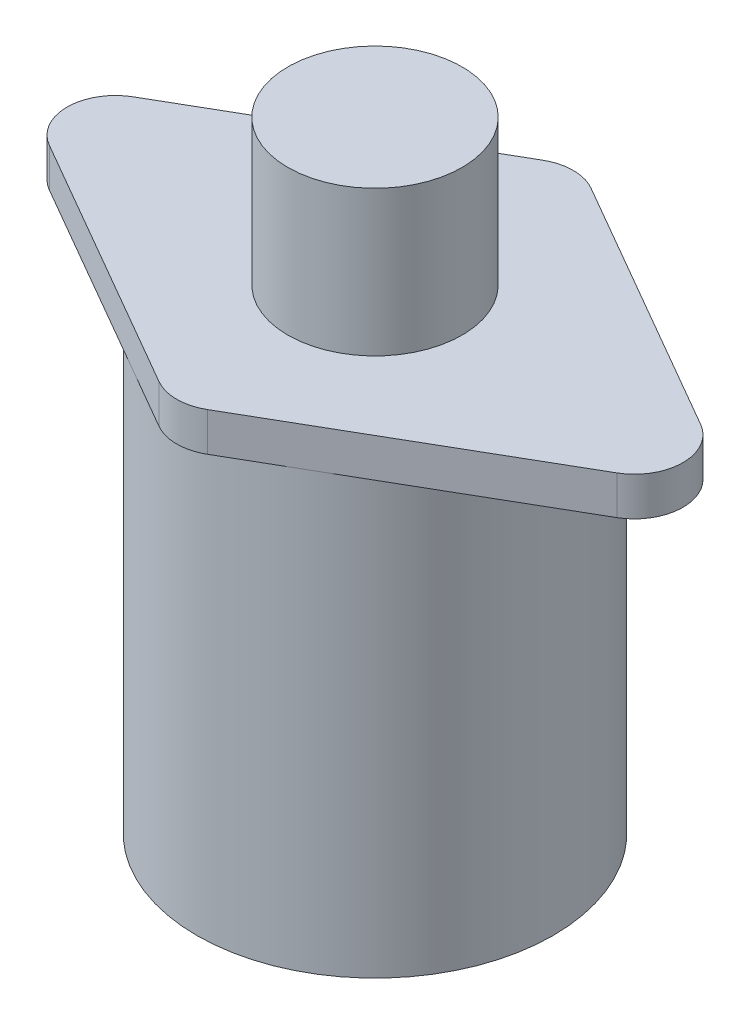
SolidWorks part; units mm, degrees
ref_plane "Alzado" through (0, 0, 0) normal (0, 0, 1) x (1, 0, 0)
ref_plane "Planta" through (0, 0, 0) normal (0, 1, 0) x (1, 0, 0)
ref_plane "Vista lateral" through (0, 0, 0) normal (1, 0, 0) x (0, 0, -1)
sketch "Sketch1" plane through (0, 0, 0) normal (0, 1, 0) x (1, 0, 0)
  circle A0 centre (0, 0) radius 18.4
  dimension "D1" = 36.8
extrude "Boss-Extrude1" add sketch "Sketch1" along normal blind 45
sketch "Sketch2" plane through (0, 45, 0) normal (0, 1, 0) x (1, 0, 0)
  line L0 (0, 21.25) -> (0, -21.25) construction
  line L1 (0, 21.25) -> (-36.8061, 0)
  line L2 (-36.8061, 0) -> (0, -21.25)
  line L3 (0, -21.25) -> (36.8061, 0)
  line L4 (36.8061, 0) -> (0, 21.25)
  dimension "D1" = 42.5
extrude "Boss-Extrude2" add sketch "Sketch2" along normal blind 4
fillet "Fillet1" radius 5 4 edges at (0, 47, -21.25) (0, 47, 21.25) (36.8061, 47, 0) (-36.8061, 47, 0)
sketch "Sketch3" plane through (0, 49, 0) normal (0, 1, 0) x (1, 0, 0)
  circle A0 centre (0, 0) radius 9
  dimension "D1" = 18
extrude "Boss-Extrude3" add sketch "Sketch3" along normal blind 15
